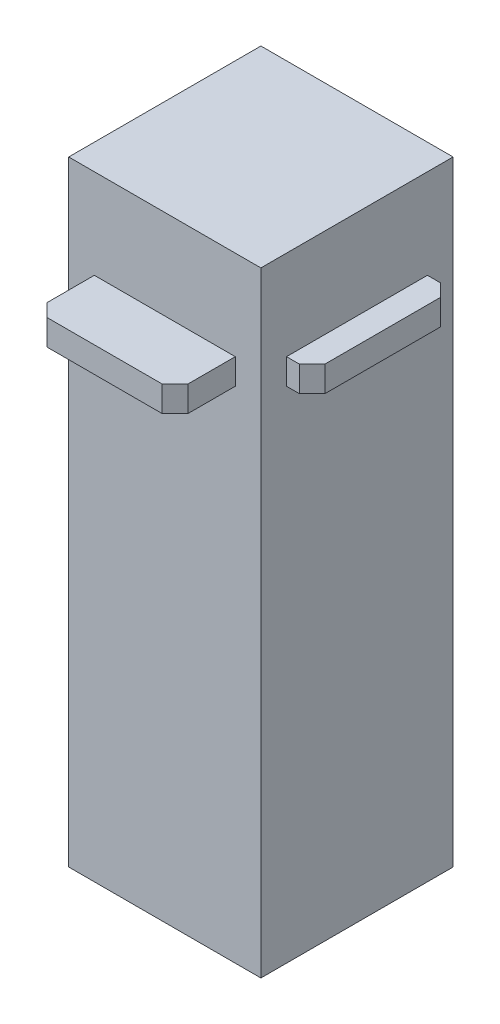
SolidWorks part; units mm, degrees
ref_plane "Front Plane" through (0, 0, 0) normal (0, 0, 1) x (1, 0, 0)
ref_plane "Top Plane" through (0, 0, 0) normal (0, 1, 0) x (1, 0, 0)
ref_plane "Right Plane" through (0, 0, 0) normal (1, 0, 0) x (0, 0, -1)
sketch "Sketch2" plane through (0, 0, 0) normal (0, 1, 0) x (1, 0, 0)
  line L1 (75, -75) -> (-75, -75)
  line L2 (75, -75) -> (75, 75)
  line L3 (75, 75) -> (-75, 75)
  line L4 (-75, -75) -> (-75, 75)
  line L5 (75, -75) -> (-75, 75) construction
  line L6 (75, 75) -> (-75, -75) construction
  line L7 (65, -65) -> (-65, -65)
  line L8 (65, -65) -> (65, 65)
  line L9 (65, 65) -> (-65, 65)
  line L10 (-65, -65) -> (-65, 65)
  line L11 (65, -65) -> (-65, 65) construction
  line L12 (65, 65) -> (-65, -65) construction
  point P0 (0, 0)
  point P6 (0, 0)
  dimension "D1" = 150
  dimension "D2" = 150
  dimension "D3" = 10
extrude "Boss-Extrude2" add sketch "Sketch2" along normal blind 450
sketch "Sketch4" plane through (0, 450, 0) normal (0, 1, 0) x (1, 0, 0)
  line L1 (75, -75) -> (-75, -75)
  line L2 (75, -75) -> (75, 75)
  line L3 (75, 75) -> (-75, 75)
  line L4 (-75, -75) -> (-75, 75)
  line L5 (75, -75) -> (-75, 75) construction
  line L6 (75, 75) -> (-75, -75) construction
  point P0 (0, 0)
extrude "Boss-Extrude3" add sketch "Sketch4" along normal blind 15
extrude "Boss-Extrude4" add sketch "Sketch4<2>" against normal blind 15 from offset 450 offset against normal yes
sketch "Sketch4<2>" plane through (0, 450, 0) normal (0, 1, 0) x (1, 0, 0) same geometry as "Sketch4"
sketch "Sketch5" plane through (0, -15, 0) normal (0, -1, 0) x (1, 0, 0)
  line L0 (-75, -75) -> (-75, 75) construction
  circle A0 centre (-35, 0) radius 30
  dimension "D1" = 40
extrude "Cut-Extrude1" cut sketch "Sketch5" against normal blind 15
sketch "Sketch7" plane through (0, 450, 0) normal (0, -1, 0) x (1, 0, 0)
  line L1 (10, -20) -> (-10, -20)
  line L2 (10, -20) -> (10, -10)
  line L3 (10, -10) -> (-10, -10)
  line L4 (-10, -20) -> (-10, -10)
  line L5 (10, -20) -> (-10, -10) construction
  line L6 (10, -10) -> (-10, -20) construction
  point P0 (0, -15)
  dimension "D1" = 10
  dimension "D2" = 10
  dimension "D3" = 20
extrude "Boss-Extrude5" add sketch "Sketch7" along normal blind 50
mirror "Mirror1" about plane through (0, 0, 0) normal (0, 0, 1) of "Boss-Extrude5"
sketch "Sketch9" plane through (0, 0, 0) normal (0, 0, 1) x (1, 0, 0)
  line L1 (10, 450) -> (-10, 450) construction
  circle A0 centre (0, 420) radius 25
  dimension "D1" = 30
extrude "Boss-Extrude6" add sketch "Sketch9" along normal blind 20 from offset 10 offset against normal yes
sketch "Sketch10" plane through (0, 0, -10) normal (0, 0, 1) x (1, 0, 0)
  line L1 (10, 450) -> (-10, 450) construction
  circle A0 centre (0, 420) radius 22
  circle A1 centre (0, 420) radius 25
  dimension "D1" = 30
extrude "Cut-Extrude3" cut sketch "Sketch10" along normal blind 10 from offset 5
sketch "Sketch12" plane through (0, 0, 0) normal (0, 1, 0) x (1, 0, 0)
  line L0 (65, 65) -> (-65, 65) construction
  line L1 (45, 23) -> (25, 23)
  line L2 (45, 23) -> (45, 63)
  line L3 (45, 63) -> (25, 63)
  line L4 (25, 23) -> (25, 63)
  line L5 (45, 23) -> (25, 63) construction
  line L6 (45, 63) -> (25, 23) construction
  line L7 (65, -65) -> (65, 65) construction
  point P0 (35, 43)
  dimension "D1" = 20
  dimension "D2" = 40
  dimension "D3" = 2
  dimension "D4" = 30
extrude "Boss-Extrude7" add sketch "Sketch12" along normal blind 25
sketch "Sketch13" plane through (0, 0, -23) normal (0, 0, 1) x (1, 0, 0)
  circle A0 centre (35.1215, 12.6107) radius 4
extrude "Boss-Extrude8" add sketch "Sketch13" along normal blind 23
sketch "Sketch18" plane through (75, 0, 0) normal (1, 0, 0) x (0, 0, -1)
  line L0 (-55, 395) -> (55, 395)
  line L1 (55, 395) -> (55, 375)
  line L2 (55, 375) -> (-55, 375)
  line L3 (-55, 375) -> (-55, 395)
  line L4 (-75, 465) -> (75, 465) construction
  point P6 (0, 395)
  point P7 (0, 465)
  dimension "D1" = 70
  dimension "D2" = 20
  dimension "D3" = 110
extrude "Boss-Extrude11" add sketch "Sketch18" along normal blind 20
chamfer "Chamfer1" distance 10 angle 45 1 edges at (95, 385, 55)
chamfer "Chamfer2" distance 10 angle 45 1 edges at (95, 385, -55)
sketch "Sketch19" plane through (0, 0, 75) normal (0, 0, 1) x (1, 0, 0)
  line L0 (-55, 395) -> (55, 395)
  line L1 (55, 395) -> (55, 375)
  line L2 (55, 375) -> (-55, 375)
  line L3 (-55, 375) -> (-55, 395)
  line L4 (-75, 465) -> (75, 465) construction
  point P6 (0, 465)
  point P7 (0, 375)
  dimension "D1" = 70
  dimension "D2" = 110
  dimension "D3" = 20
extrude "Boss-Extrude12" add sketch "Sketch19" along normal blind 47
chamfer "Chamfer3" distance 10 angle 45 2 edges at (-55, 385, 122) (55, 385, 122)
